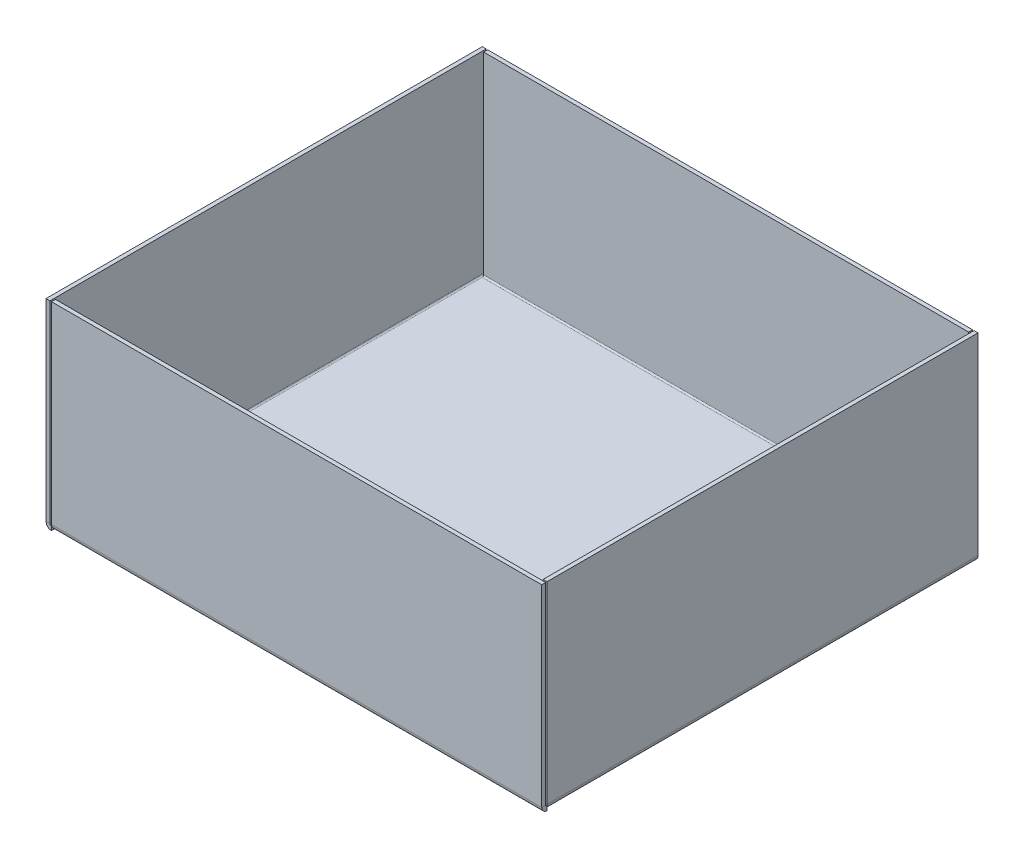
SolidWorks part; units mm, degrees
note: The reader was unsure of these and kept them because the rebuilt part matched: flange length of "边线-法兰1", "边线-法兰2", "边线-法兰3", "边线-法兰4".
ref_plane "前视基准面" through (0, 0, 0) normal (0, 0, 1) x (1, 0, 0)
ref_plane "上视基准面" through (0, 0, 0) normal (0, 1, 0) x (1, 0, 0)
ref_plane "右视基准面" through (0, 0, 0) normal (1, 0, 0) x (0, 0, -1)
other "Configuration Table"
sketch "草图1" plane through (0, 0, 0) normal (0, 1, 0) x (1, 0, 0)
  line L1 (-125, -110) -> (125, -110)
  line L2 (-125, -110) -> (-125, 110)
  line L3 (-125, 110) -> (125, 110)
  line L4 (125, -110) -> (125, 110)
  line L5 (-125, -110) -> (125, 110) construction
  line L6 (-125, 110) -> (125, -110) construction
  point P0 (0, 0)
  dimension "D1" = 250
  dimension "D2" = 220
base flange "基体-法兰1" sketch "草图1" thickness 2 reverse thickness direction no parameters "D1"=0.7366
edge flange "边线-法兰1" sketch "草图4" flange angle 90 flange length 100 flange position material inside bend radius 0.7366 thickness 2 relief rectangular parameters "D6"=10
sketch "草图4" plane through (-125, 0, 0) normal (1, 0, 0) x (0, 0, -1)
  line L2 (-110, 0) -> (-110, 98)
  line L3 (-110, 98) -> (110, 98)
  line L4 (110, 98) -> (110, 0)
  line L5 (110, 0) -> (-110, 0) construction
  line L6 (110, 0) -> (-110, 0)
bend "边线折弯1" bend radius 0.7366 bend angle 90 parameters "D5"=1
edge flange "边线-法兰2" sketch "草图7" flange angle 90 flange length 100 flange position material inside bend radius 0.7366 thickness 2 relief none parameters "D6"=10
sketch "草图7" plane through (0, 0, 110) normal (0, 0, -1) x (-1, 0, 0)
  line L2 (-125, 0) -> (-125, 98)
  line L3 (-125, 98) -> (122.2634, 98)
  line L4 (122.2634, 98) -> (122.2634, 0)
  line L5 (122.2634, 0) -> (-125, 0) construction
  line L6 (122.2634, 0) -> (-125, 0)
bend "边线折弯2" bend radius 0.7366 bend angle 90 parameters "D5"=2
edge flange "边线-法兰3" sketch "草图10" flange angle 90 flange length 100 flange position material inside bend radius 0.7366 thickness 2 relief none parameters "D6"=10
sketch "草图10" plane through (125, 0, 0) normal (-1, 0, 0) x (0, 0, 1)
  line L2 (-110, 0) -> (-110, 98)
  line L3 (-110, 98) -> (107.2634, 98)
  line L4 (107.2634, 98) -> (107.2634, 0)
  line L5 (107.2634, 0) -> (-110, 0) construction
  line L6 (107.2634, 0) -> (-110, 0)
bend "边线折弯3" bend radius 0.7366 bend angle 90 parameters "D5"=3
edge flange "边线-法兰4" sketch "草图13" flange angle 90 flange length 100 flange position material inside bend radius 0.7366 thickness 2 relief none parameters "D6"=10
sketch "草图13" plane through (0, 0, -110) normal (0, 0, 1) x (1, 0, 0)
  line L2 (-122.2634, 0) -> (-122.2634, 98)
  line L3 (-122.2634, 98) -> (122.2634, 98)
  line L4 (122.2634, 98) -> (122.2634, 0)
  line L5 (122.2634, 0) -> (-122.2634, 0) construction
  line L6 (122.2634, 0) -> (-122.2634, 0)
bend "边线折弯4" bend radius 0.7366 bend angle 90 parameters "D5"=4
sketch "折弯-线1" plane through (0, 0, 0) normal (0, 1, 0) x (1, 0, 0)
sketch "边界框1" plane through (0, 0, 0) normal (0, 1, 0) x (1, 0, 0)
sheet metal parameters "钣金6" thickness 2 parameters "D1"=0.7366
flat pattern "平板型式6" [suppressed]
sketch "折弯-线2" plane through (0, 0, 0) normal (0, 1, 0) x (1, 0, 0)
sketch "边界框2" [suppressed] plane through (0, 0, 0) normal (0, 1, 0) x (1, 0, 0)
sheet metal parameters "钣金7" thickness 2 parameters "D1"=0.7366
flat pattern "平板型式6" [suppressed]
sketch "折弯-线2" plane through (0, 0, 0) normal (0, 1, 0) x (1, 0, 0)
sketch "边界框2" [suppressed] plane through (0, 0, 0) normal (0, 1, 0) x (1, 0, 0)
bend of the flat pattern "展平-<边线折弯1>1"
sheet metal parameters "钣金8" thickness 2 parameters "D1"=0.7366
flat pattern "平板型式6" [suppressed]
sketch "折弯-线2" plane through (0, 0, 0) normal (0, 1, 0) x (1, 0, 0)
sketch "边界框2" [suppressed] plane through (0, 0, 0) normal (0, 1, 0) x (1, 0, 0)
bend of the flat pattern "展平-<边线折弯1>1"
bend of the flat pattern "展平-<边线折弯2>1"
sheet metal parameters "钣金9" thickness 2 parameters "D1"=0.7366
flat pattern "平板型式6" [suppressed]
sketch "折弯-线2" plane through (0, 0, 0) normal (0, 1, 0) x (1, 0, 0)
sketch "边界框2" [suppressed] plane through (0, 0, 0) normal (0, 1, 0) x (1, 0, 0)
bend of the flat pattern "展平-<边线折弯1>1"
bend of the flat pattern "展平-<边线折弯2>1"
bend of the flat pattern "展平-<边线折弯3>1"
sheet metal parameters "钣金10" thickness 2 parameters "D1"=0.7366
flat pattern "平板型式6" [suppressed]
sketch "折弯-线2" plane through (0, 0, 0) normal (0, 1, 0) x (1, 0, 0)
sketch "边界框2" [suppressed] plane through (0, 0, 0) normal (0, 1, 0) x (1, 0, 0)
bend of the flat pattern "展平-<边线折弯1>1"
bend of the flat pattern "展平-<边线折弯2>1"
bend of the flat pattern "展平-<边线折弯3>1"
bend of the flat pattern "展平-<边线折弯4>1"
